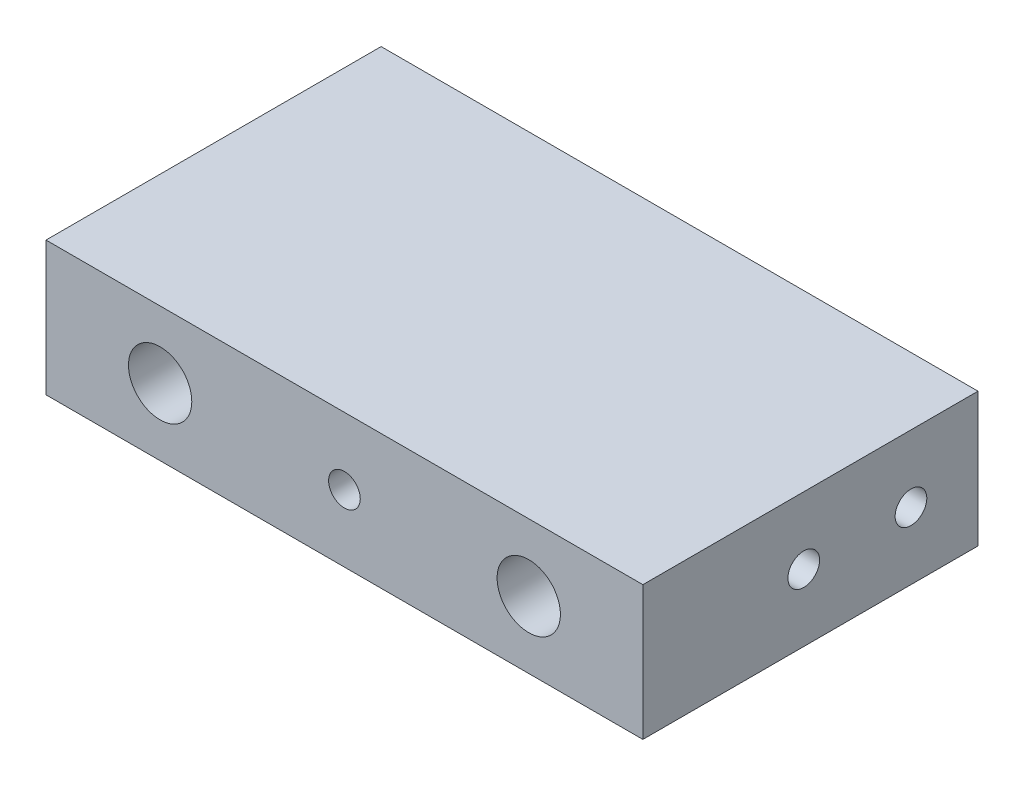
SolidWorks part; units mm, degrees
material "ABS"
ref_plane "X-Y Datum" through (0, 0, 0) normal (0, 0, 1) x (1, 0, 0)
ref_plane "X-Z Datum" through (0, 0, 0) normal (0, 1, 0) x (1, 0, 0)
ref_plane "Y-Z Datum" through (0, 0, 0) normal (1, 0, 0) x (0, 0, -1)
sketch "Sketch1" plane through (0, 0, 0) normal (0, 0, 1) x (1, 0, 0)
  line L1 (-28.275, 6.35) -> (28.275, 6.35)
  line L2 (-28.275, 6.35) -> (-28.275, -6.35)
  line L3 (-28.275, -6.35) -> (28.275, -6.35)
  line L4 (28.275, 6.35) -> (28.275, -6.35)
  line L5 (-28.275, 6.35) -> (28.275, -6.35) construction
  line L6 (-28.275, -6.35) -> (28.275, 6.35) construction
  point P0 (0, 0)
  dimension "D1" = 56.55
  dimension "D2" = 12.7
extrude "Boss-Extrude1" add sketch "Sketch1" along normal blind 31.75 contours L2 L3 L4 L1
sketch "Sketch2" plane through (0, 0, 31.75) normal (0, 0, 1) x (1, 0, 0)
  line L0 (-28.275, 0) -> (28.275, 0) construction
  line L1 (-28.275, 6.35) -> (-28.275, -6.35) construction
  line L2 (28.275, 6.35) -> (28.275, -6.35) construction
  line L3 (-17.4625, 0) -> (17.4625, 0) construction
  circle A0 centre (17.4625, 0) radius 3
  circle A1 centre (-17.4625, 0) radius 3
  circle A2 centre (0, 0) radius 1.5
  point P10 (0, 0)
  dimension "D1" = 6
  dimension "D3" = 3
  dimension "D2" = 34.925
extrude "Cut-Extrude1" cut sketch "Sketch2" against normal blind 10 contours A1 L0 L3 | L0 A1 L3 | L0 L3 A0 | L3 L0 A0 | A2 region at (17.4625, 0, 31.75) region at (-17.4625, 0, 31.75) region at (0, 0, 31.75)
sketch "Sketch3" plane through (-28.275, 0, 0) normal (-1, 0, 0) x (0, 0, 1)
  line L0 (31.75, 0) -> (0, 0) construction
  line L1 (31.75, 6.35) -> (31.75, -6.35) construction
  line L2 (0, 6.35) -> (0, -6.35) construction
  circle A0 centre (6.35, 0) radius 1.5
  circle A1 centre (16.51, 0) radius 1.5
  dimension "D1" = 3
  dimension "D2" = 10.16
  dimension "D3" = 6.35
extrude "Cut-Extrude2" cut sketch "Sketch3" against normal through all contours A0 L0 | L0 A0 | A1 L0 | L0 A1 region at (-28.275, -0.6366, 16.51) region at (-28.275, 0.6366, 16.51) region at (-28.275, -0.6366, 6.35) region at (-28.275, 0.6366, 6.35)
